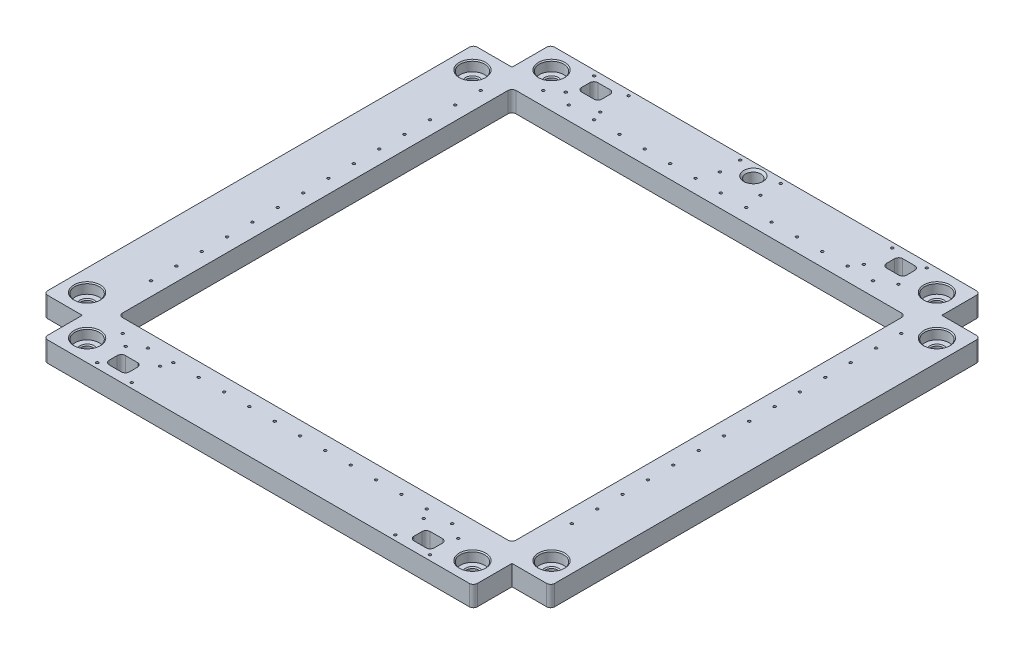
SolidWorks part; units mm, degrees
material "ASTM A36 Steel"
ref_plane "Front Plane" through (0, 0, 0) normal (0, 0, 1) x (1, 0, 0)
ref_plane "Top Plane" through (0, 0, 0) normal (0, 1, 0) x (1, 0, 0)
ref_plane "Right Plane" through (0, 0, 0) normal (1, 0, 0) x (0, 0, -1)
sketch "Sketch1" plane through (0, 0, 0) normal (0, 1, 0) x (1, 0, 0)
  line L1 (250, -250) -> (-250, -250)
  line L2 (250, -250) -> (250, 250)
  line L3 (250, 250) -> (-250, 250)
  line L4 (-250, -250) -> (-250, 250)
  line L5 (250, -250) -> (-250, 250) construction
  line L6 (250, 250) -> (-250, -250) construction
  point P0 (0, 0)
  dimension "D1" = 500
  dimension "D2" = 500
extrude "Boss-Extrude1" add sketch "Sketch1" along normal blind 20
sketch "Sketch2" plane through (0, 20, 0) normal (0, 1, 0) x (1, 0, 0)
  line L0 (250, 250) -> (-250, 250) construction
  line L10 (-250, 250) -> (-250, -250) construction
  line L15 (-250, 169) -> (-208, 169)
  line L16 (-250, 169) -> (-250, 211)
  line L17 (-174.5, 213.5) -> (-205.5, 213.5)
  line L27 (-250, 211) -> (-208, 211)
  line L33 (-208, 169) -> (-208, 211)
  line L35 (-250, 169) -> (-208, 211) construction
  line L36 (-250, 211) -> (-208, 169) construction
  line L37 (-169, 208) -> (-211, 208)
  line L38 (-169, 208) -> (-169, 250)
  line L39 (-169, 250) -> (-211, 250)
  line L40 (-211, 208) -> (-211, 250)
  line L41 (-169, 208) -> (-211, 250) construction
  line L42 (-169, 250) -> (-211, 208) construction
  line L43 (-208, 206) -> (-213, 211)
  line L44 (-174.5, 213.5) -> (-174.5, 244.5)
  line L45 (-174.5, 244.5) -> (-205.5, 244.5)
  line L46 (-205.5, 213.5) -> (-205.5, 244.5)
  line L47 (-174.5, 213.5) -> (-205.5, 244.5) construction
  line L48 (-174.5, 244.5) -> (-205.5, 213.5) construction
  line L49 (-213.5, 174.5) -> (-244.5, 174.5)
  line L50 (-213.5, 174.5) -> (-213.5, 205.5)
  line L51 (-213.5, 205.5) -> (-244.5, 205.5)
  line L52 (-244.5, 174.5) -> (-244.5, 205.5)
  line L53 (-213.5, 174.5) -> (-244.5, 205.5) construction
  line L54 (-213.5, 205.5) -> (-244.5, 174.5) construction
  line L55 (-206, 208) -> (-211, 213)
  line L56 (-213, 211) -> (-211, 213) construction
  point P1 (-229, 190)
  point P5 (-190, 229)
  point P23 (-229, 190)
  point P27 (-190, 229)
  dimension "D1" = 5
  dimension "D2" = 45
  dimension "D3" = 42
  dimension "D4" = 31
  dimension "D5" = 45
  dimension "D6" = 5
  dimension "D7" = 60
hole_wizard "Bearing Press Fit" positions "Sketch8" profile "Sketch9" hole size "Ø12.0" standard "ANSI Metric" end condition through all
sketch "Sketch8" plane through (0, 20, 0) normal (0, 1, 0) x (1, 0, 0)
  line L1 (-169, 250) -> (-211, 208) construction
  point P8 (-190, 229)
  point P12 (-229, 190)
sketch "Sketch9" plane through (-190, 20, -229) normal (1, 0, 0) x (0, 0, 1)
  line L0 (0, 0) -> (0, 20)
  line L1 (0, 20) -> (6, 20)
  line L2 (6, 20) -> (6, 0)
  line L5 (6, 0) -> (0, 0)
  line L11 (0, -6.35) -> (0, 107.95) construction
  dimension "Thru Hole Dia." = 12
  dimension "Thru Hole Depth" = 20
ref_axis "Axis1" through (0, 21, 0) along (0, -1, 0)
pattern_circular "CirPattern1" count 4 over 360 about axis through (0, 21, 0) along (0, -1, 0) of "Bearing Press Fit"
sketch "Sketch5" plane through (0, 20, 0) normal (0, 1, 0) x (1, 0, 0)
  line L1 (194, -194) -> (-194, -194)
  line L2 (194, -194) -> (194, 194)
  line L3 (194, 194) -> (-194, 194)
  line L4 (-194, -194) -> (-194, 194)
  line L5 (194, -194) -> (-194, 194) construction
  line L6 (194, 194) -> (-194, -194) construction
  point P0 (0, 0)
  dimension "D1" = 388
extrude "Cut-Extrude1" cut sketch "Sketch5" against normal up to surface (20 mm away) up to face at (-229, 0, 196)
sketch "Sketch10" plane through (0, 0, 0) normal (0, 1, 0) x (1, 0, 0)
  line L5 (194, 194) -> (-194, 194) construction
  line L6 (214, -214) -> (-214, -214)
  line L14 (214, -214) -> (214, 214)
  line L15 (214, 214) -> (-214, 214)
  line L16 (-214, -214) -> (-214, 214)
  line L17 (214, -214) -> (-214, 214) construction
  line L18 (214, 214) -> (-214, -214) construction
  line L19 (201.5, -201.5) -> (-201.5, -201.5)
  line L20 (201.5, -201.5) -> (201.5, 201.5)
  line L21 (201.5, 201.5) -> (-201.5, 201.5)
  line L22 (-201.5, -201.5) -> (-201.5, 201.5)
  line L23 (201.5, -201.5) -> (-201.5, 201.5) construction
  line L24 (201.5, 201.5) -> (-201.5, -201.5) construction
  point P0 (0, 0)
  point P6 (0, 0)
  dimension "D2" = 7.5
  dimension "D1" = 12.5
extrude "Linear Rail Slot" cut sketch "Sketch10" along normal blind 2.5
fillet "Fillet2" radius 4 4 edges at (-194, 10, 194) (194, 10, 194) (194, 10, -194) (-194, 10, -194)
sketch "Sketch11" plane through (0, 2.5, 0) normal (0, -1, 0) x (1, 0, 0)
  line L0 (-194, 207.5) -> (166, 207.5)
  line L1 (-201.5, 201.5) -> (201.5, 201.5) construction
  line L3 (-214, -214) -> (-214, 214) construction
  point P16 (148.5, 207.5)
  point P18 (123.5, 207.5)
  point P19 (98.5, 207.5)
  point P20 (73.5, 207.5)
  point P21 (48.5, 207.5)
  point P22 (23.5, 207.5)
  point P23 (-1.5, 207.5)
  point P24 (-26.5, 207.5)
  point P25 (-51.5, 207.5)
  point P26 (-76.5, 207.5)
  point P28 (-101.5, 207.5)
  point P29 (-126.5, 207.5)
  point P30 (-151.5, 207.5)
  point P31 (-176.5, 207.5)
  dimension "D1" = 360
  dimension "D2" = 6
  dimension "D4" = 14
  dimension "D5" = 25
  dimension "D6" = 20
  dimension "D3" = 17.5
hole_wizard "Tap Drill for M3x0.5 Tap1" positions "Sketch12" profile "Sketch13" hole size "M3x0.5" standard "ANSI Metric" end condition through all
sketch "Sketch12" plane through (0, 2.5, 0) normal (0, -1, 0) x (-1, 0, 0)
  line L0 (194, -207.5) -> (-166, -207.5) construction
  point P28 (-148.5, -207.5)
  point P31 (-123.5, -207.5)
  point P34 (-98.5, -207.5)
  point P37 (-73.5, -207.5)
  point P40 (-48.5, -207.5)
  point P43 (-23.5, -207.5)
  point P46 (1.5, -207.5)
  point P49 (26.5, -207.5)
  point P51 (51.5, -207.5)
  point P54 (76.5, -207.5)
  point P57 (101.5, -207.5)
  point P61 (126.5, -207.5)
  point P64 (151.5, -207.5)
  point P67 (176.5, -207.5)
sketch "Sketch13" plane through (148.5, 2.5, 207.5) normal (1, 0, 0) x (0, 0, -1)
  line L0 (0, 0) -> (0, 17.5)
  line L1 (0, 17.5) -> (1.25, 17.5)
  line L2 (1.25, 17.5) -> (1.25, 0)
  line L5 (1.25, 0) -> (0, 0)
  line L11 (0, -6.35) -> (0, 107.95) construction
  dimension "Thru Hole Dia." = 2.5
  dimension "Thru Hole Depth" = 17.5
sketch "Sketch14" plane through (0, 0, 0) normal (0, -1, 0) x (1, 0, 0)
  line L1 (-151.5, 213.5) -> (-176.5, 213.5)
  line L2 (-147.5, 217.5) -> (-147.5, 219.5)
  line L3 (-151.5, 223.5) -> (-176.5, 223.5)
  line L4 (-180.5, 217.5) -> (-180.5, 219.5)
  line L5 (-147.5, 213.5) -> (-180.5, 223.5) construction
  line L6 (-147.5, 223.5) -> (-180.5, 213.5) construction
  line L7 (-201.5, 201.5) -> (201.5, 201.5) construction
  line L8 (-176.5, 207.5) -> (-151.5, 207.5) construction
  line L19 (-1.5, 213.5) -> (-26.5, 213.5)
  line L25 (2.5, 217.5) -> (2.5, 219.5)
  line L26 (-1.5, 223.5) -> (-26.5, 223.5)
  line L31 (-30.5, 217.5) -> (-30.5, 219.5)
  line L32 (2.5, 213.5) -> (-30.5, 223.5) construction
  line L33 (2.5, 223.5) -> (-30.5, 213.5) construction
  line L34 (-26.5, 207.5) -> (-1.5, 207.5) construction
  line L35 (148.5, 213.5) -> (123.5, 213.5)
  line L36 (152.5, 217.5) -> (152.5, 219.5)
  line L37 (148.5, 223.5) -> (123.5, 223.5)
  line L38 (119.5, 217.5) -> (119.5, 219.5)
  line L39 (152.5, 213.5) -> (119.5, 223.5) construction
  line L40 (152.5, 223.5) -> (119.5, 213.5) construction
  line L41 (123.5, 207.5) -> (148.5, 207.5) construction
  arc A3 (-147.5, 219.5) -> (-151.5, 223.5) centre (-151.5, 219.5) ccw
  arc A4 (-151.5, 213.5) -> (-147.5, 217.5) centre (-151.5, 217.5) ccw
  arc A5 (-176.5, 213.5) -> (-180.5, 217.5) centre (-176.5, 217.5) cw
  arc A6 (-176.5, 223.5) -> (-180.5, 219.5) centre (-176.5, 219.5) ccw
  arc A7 (2.5, 219.5) -> (-1.5, 223.5) centre (-1.5, 219.5) ccw
  arc A8 (-1.5, 213.5) -> (2.5, 217.5) centre (-1.5, 217.5) ccw
  arc A9 (-26.5, 213.5) -> (-30.5, 217.5) centre (-26.5, 217.5) cw
  arc A10 (-26.5, 223.5) -> (-30.5, 219.5) centre (-26.5, 219.5) ccw
  arc A11 (152.5, 219.5) -> (148.5, 223.5) centre (148.5, 219.5) ccw
  arc A12 (148.5, 213.5) -> (152.5, 217.5) centre (148.5, 217.5) ccw
  arc A13 (123.5, 213.5) -> (119.5, 217.5) centre (123.5, 217.5) cw
  arc A14 (123.5, 223.5) -> (119.5, 219.5) centre (123.5, 219.5) ccw
  point P0 (-164, 218.5)
  point P12 (-164, 207.5)
  point P26 (-14, 218.5)
  point P45 (136, 218.5)
  dimension "D5" = 3
  dimension "D4" = 4
  dimension "D1" = 33
  dimension "D2" = 12
  dimension "D3" = 10
  dimension "D7" = 25
  dimension "D6" = 150
mirror "Mirror5" about plane through (0, 0, 0) normal (0, 0, 1) of "Tap Drill for M3x0.5 Tap1"
ref_plane "Plane1" through (0, 0, 0) normal (-0.7071, 0, 0.7071) x (0.7071, 0, 0.7071)
mirror "Mirror6" about plane through (0, 0, 0) normal (-0.7071, 0, 0.7071) of "Mirror5"
sketch "Sketch19" plane through (0, 2.5, 0) normal (0, -1, 0) x (1, 0, 0)
  line L0 (-198.5, 201.5) -> (-198.5, 214)
  line L1 (-201.5, 201.5) -> (201.5, 201.5) construction
  line L2 (-214, 214) -> (214, 214) construction
  line L3 (-198.5, 214) -> (-214, 214)
  line L4 (-214, 214) -> (-214, 198.5)
  line L5 (-214, -214) -> (-214, 214) construction
  line L6 (-214, 198.5) -> (-201.5, 198.5)
  line L7 (-201.5, -201.5) -> (-201.5, 201.5) construction
  line L8 (-201.5, 198.5) -> (-201.5, 201.5)
  line L9 (-201.5, 201.5) -> (-198.5, 201.5)
  dimension "D1" = 3
extrude "Boss-Extrude2" add sketch "Sketch19" along normal up to surface (2.5 mm away) up to face at (-229, 0, 196)
pattern_circular "CirPattern4" count 4 over 360 about axis through (0, 21, 0) along (0, -1, 0) of "Boss-Extrude2"
sketch "Sketch20" plane through (0, 20, 0) normal (0, 1, 0) x (1, 0, 0)
  line L5 (-250, -250) -> (250, -250) construction
  line L20 (140.3, -225) -> (160.3, -241) construction
  line L23 (160.3, -225) -> (140.3, -241) construction
  line L28 (114, -247) -> (164, -219) construction
  line L29 (164, -247) -> (114, -219) construction
  line L30 (164, -219) -> (114, -219) construction
  line L31 (114, -247) -> (114, -219) construction
  line L32 (164, -247) -> (114, -247) construction
  line L33 (164, -247) -> (164, -219) construction
  line L34 (156.3, -241) -> (144.3, -241)
  line L35 (140.3, -229) -> (140.3, -237)
  line L36 (156.3, -225) -> (144.3, -225)
  line L37 (160.3, -229) -> (160.3, -237)
  arc A12 (144.3, -225) -> (140.3, -229) centre (144.3, -229) ccw
  arc A13 (140.3, -237) -> (144.3, -241) centre (144.3, -237) ccw
  arc A14 (160.3, -237) -> (156.3, -241) centre (156.3, -237) cw
  arc A15 (160.3, -229) -> (156.3, -225) centre (156.3, -229) ccw
  circle A16 centre (190, -229) radius 6 construction
  point P65 (150.3, -233)
  point P66 (139, -233)
  point P67 (139, -233)
  dimension "D7" = 39.7
  dimension "D8" = 11.3
  dimension "D6" = 4
  dimension "D1" = 28
  dimension "D2" = 50
  dimension "D3" = 17
  dimension "D4" = 20
  dimension "D5" = 16
extrude "Cut-Extrude3" cut sketch "Sketch20" against normal through all
hole_wizard "Tap Drill for M3x0.5 Tap6" positions "Sketch39" profile "Sketch40" hole size "M3x0.5" standard "ANSI Metric"
sketch "Sketch39" plane through (0, 20, 0) normal (0, 1, 0) x (1, 0, 0)
  line L1 (164, -245) -> (130, -245)
  line L2 (164, -245) -> (164, -217)
  line L3 (164, -217) -> (130, -217)
  line L4 (130, -245) -> (130, -217)
  line L5 (-250, -250) -> (250, -250) construction
  circle A0 centre (190, -229) radius 6 construction
  point P1 (164, -245)
  point P2 (130, -217)
  point P99 (164, -217)
  point P100 (130, -245)
  dimension "D1" = 34
  dimension "D2" = 28
  dimension "D3" = 5
  dimension "D4" = 26
sketch "Sketch40" plane through (164, 20, 245) normal (1, 0, 0) x (0, 0, 1)
  line L0 (0, 0) -> (0, 20)
  line L1 (0, 20) -> (1.25, 20)
  line L2 (1.25, 20) -> (1.25, 0)
  line L5 (1.25, 0) -> (0, 0)
  line L10 (0, 20) -> (-1.25, 20) construction
  line L11 (0, -6.35) -> (0, 107.95) construction
  dimension "Hole Dia." = 2.5
  dimension "Hole Depth" = 20
  dimension "Drill Angle" = 180
mirror "Mirror8" about plane through (0, 0, 0) normal (1, 0, 0) of "Tap Drill for M3x0.5 Tap6", "Cut-Extrude3"
mirror "Mirror9" about plane through (0, 0, 0) normal (0, 0, 1) of "Mirror8"
sketch "Sketch27" plane through (0, 20, 0) normal (0, 1, 0) x (1, 0, 0)
  line L1 (250, -250) -> (211.9, -250)
  line L2 (250, -250) -> (250, -211.9)
  line L3 (250, -211.9) -> (211.9, -211.9)
  line L4 (211.9, -250) -> (211.9, -211.9)
  dimension "D1" = 38.1
extrude "Cut-Extrude4" cut sketch "Sketch27" against normal up to surface (20 mm away) up to face at (164, 0, -243.75)
pattern_circular "CirPattern3" count 4 over 360 about axis through (0, 21, 0) along (0, -1, 0) of "Cut-Extrude4"
fillet "Fillet5" radius 4 16 edges at (198.5, 1.25, 214) (198.5, 1.25, 201.5) (201.5, 1.25, 198.5) (214, 1.25, 198.5) (-214, 1.25, 198.5) (-198.5, 1.25, 214) (-201.5, 1.25, 198.5) (-198.5, 1.25, 201.5) (-214, 1.25, -198.5) (-198.5, 1.25, -214) (-198.5, 1.25, -201.5) (-201.5, 1.25, -198.5) (198.5, 1.25, -201.5) (198.5, 1.25, -214) (201.5, 1.25, -198.5) (214, 1.25, -198.5)
hole_wizard "Tap Drill for M3x0.5 Tap4" positions "Sketch35" profile "Sketch36" hole size "M3x0.5" standard "ANSI Metric" end condition up to next
sketch "Sketch35" plane through (0, 20, 0) normal (0, 1, 0) x (1, 0, 0)
  line L1 (20, 225) -> (-20, 225)
  line L2 (20, 225) -> (20, 245)
  line L3 (20, 245) -> (-20, 245)
  line L4 (-20, 225) -> (-20, 245)
  line L5 (20, 225) -> (-20, 245) construction
  line L6 (20, 245) -> (-20, 225) construction
  line L7 (211.9, 250) -> (-211.9, 250) construction
  point P2 (-20, 245)
  point P53 (20, 225)
  point P54 (20, 245)
  point P55 (-20, 225)
  point P69 (0, 235)
  dimension "D1" = 20
  dimension "D2" = 40
  dimension "D3" = 15
sketch "Sketch36" plane through (-20, 20, -245) normal (1, 0, 0) x (0, 0, 1)
  line L0 (0, 0) -> (0, 20)
  line L1 (0, 20) -> (1.25, 20)
  line L2 (1.25, 20) -> (1.25, 0)
  line L5 (1.25, 0) -> (0, 0)
  line L11 (0, -6.35) -> (0, 107.95) construction
  dimension "Thru Hole Dia." = 2.5
  dimension "Thru Hole Depth" = 20
hole_wizard "Ø15.0 (15) Diameter Hole2" positions "Sketch37" profile "Sketch38" hole size "Ø15.0" standard "ANSI Metric" end condition up to next
sketch "Sketch37" plane through (0, 20, 0) normal (0, 1, 0) x (1, 0, 0)
  circle A0 centre (0, 235) radius 1.25 construction
  point P0 (0, 238)
  dimension "D1" = 3
sketch "Sketch38" plane through (0, 20, -238) normal (1, 0, 0) x (0, 0, 1)
  line L0 (0, 0) -> (0, 20)
  line L1 (0, 20) -> (7.5, 20)
  line L2 (7.5, 20) -> (7.5, 0)
  line L5 (7.5, 0) -> (0, 0)
  line L11 (0, -6.35) -> (0, 107.95) construction
  dimension "Thru Hole Dia." = 15
  dimension "Thru Hole Depth" = 20
chamfer "Chamfer1" distance 2 angle 45 2 edges at (0, 0, -230.5) (0, 20, -230.5)
hole_wizard "Ø24.0 (24) Diameter Hole1" positions "Sketch41" profile "Sketch42" hole size "Ø24.0" standard "ANSI Metric"
sketch "Sketch41" plane through (0, 20, 0) normal (0, 1, 0) x (1, 0, 0)
  point P0 (-229, -190)
  point P3 (-190, -229)
  point P6 (190, -229)
  point P9 (229, -190)
  point P12 (229, 190)
  point P15 (190, 229)
  point P18 (-190, 229)
  point P21 (-229, 190)
sketch "Sketch42" plane through (-229, 20, 190) normal (1, 0, 0) x (0, 0, 1)
  line L0 (0, 0) -> (0, 10)
  line L1 (0, 10) -> (12, 10)
  line L2 (12, 10) -> (12, 0)
  line L5 (12, 0) -> (0, 0)
  line L10 (0, 10) -> (-12, 10) construction
  line L11 (0, -6.35) -> (0, 107.95) construction
  dimension "Hole Dia." = 24
  dimension "Hole Depth" = 10
  dimension "Drill Angle" = 180
chamfer "Chamfer2" distance 1 angle 45 24 edges at (-229, 0, -184) (-229, 10, -196) (-190, 0, -223) (-190, 10, -235) (229, 0, -184) (229, 10, -196) (190, 0, -223) (190, 10, -235) (229, 0, 196) (229, 10, 184) (190, 0, 235) (190, 10, 223) (-190, 0, 235) (-190, 10, 223) (-229, 0, 196) (-229, 10, 184) (-229, 20, -178) (-190, 20, -217) (229, 20, -178) (190, 20, -217) (229, 20, 202) (190, 20, 241) (-190, 20, 241) (-229, 20, 202)
fillet "Fillet6" radius 4 8 edges at (250, 10, -211.9) (211.9, 10, -250) (-211.9, 10, -250) (-250, 10, -211.9) (211.9, 10, 250) (250, 10, 211.9) (-211.9, 10, 250) (-250, 10, 211.9)
